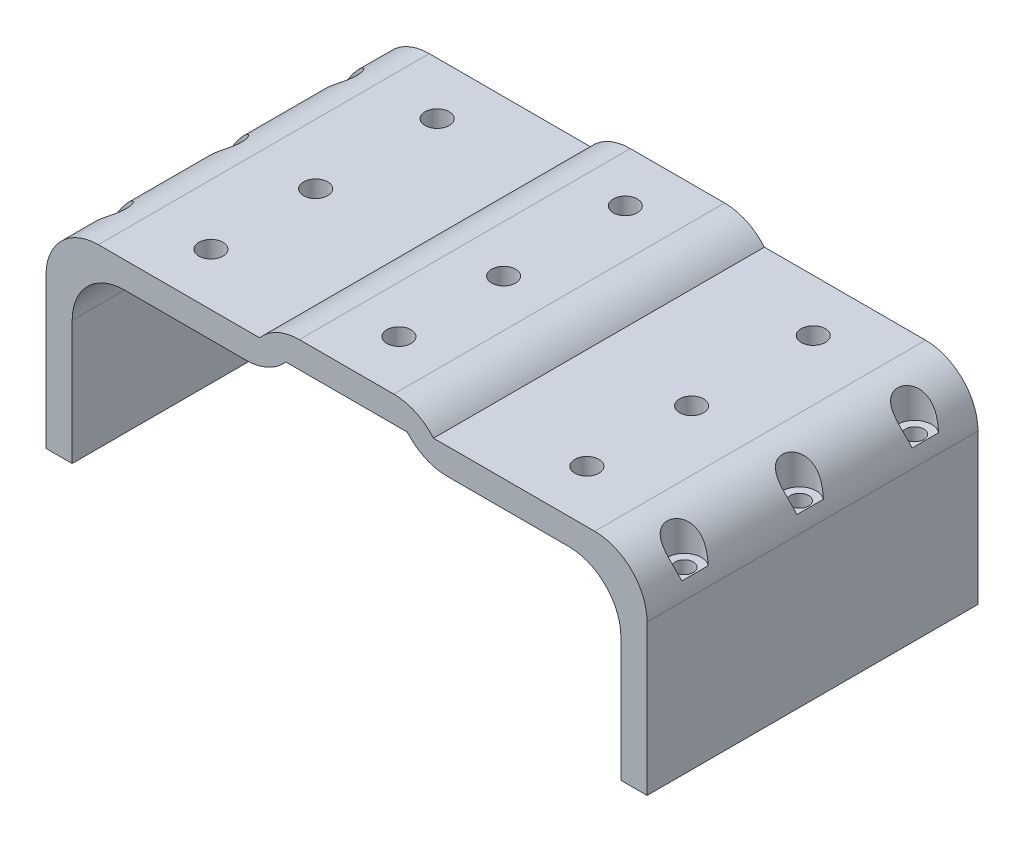
SolidWorks part; units mm, degrees
ref_plane "Front Plane" through (0, 0, 0) normal (0, 0, 1) x (1, 0, 0)
ref_plane "Top Plane" through (0, 0, 0) normal (0, 1, 0) x (1, 0, 0)
ref_plane "Right Plane" through (0, 0, 0) normal (1, 0, 0) x (0, 0, -1)
sketch "Sketch1" plane through (0, 0, 0) normal (0, 0, 1) x (1, 0, 0)
  line L5 (114.8, 0) -> (114.8, 22.5)
  line L7 (0, 22.5) -> (0, 0)
  line L8 (22.5, 22.5) -> (0, 22.5)
  line L9 (22.5, 22.5) -> (40.7918, 22.5)
  line L10 (40.7918, 22.5) -> (40.7918, 26)
  line L11 (40.7918, 26) -> (74.0082, 26)
  line L12 (74.0082, 26) -> (74.0082, 22.5)
  line L13 (74.0082, 22.5) -> (92.3, 22.5)
  line L14 (92.3, 22.5) -> (114.8, 22.5)
  line L15 (5, 0) -> (5, 17.5)
  line L16 (5, 17.5) -> (22.5, 17.5)
  line L17 (22.5, 17.5) -> (45.7918, 17.5)
  line L18 (45.7918, 17.5) -> (45.7918, 21)
  line L19 (45.7918, 21) -> (57.4, 21)
  line L20 (57.4, 21) -> (69.0082, 21)
  line L21 (69.0082, 21) -> (69.0082, 17.5)
  line L22 (69.0082, 17.5) -> (92.3, 17.5)
  line L23 (92.3, 17.5) -> (109.8, 17.5)
  line L24 (109.8, 17.5) -> (109.8, 0)
  line L25 (5, 0) -> (109.8, 0) construction
  line L26 (114.8, 0) -> (114.8, -16.2)
  line L27 (114.8, -16.2) -> (109.8, -16.2)
  line L28 (109.8, -16.2) -> (109.8, 0)
  line L29 (5, 0) -> (5, -16.2)
  line L30 (5, -16.2) -> (0, -16.2)
  line L31 (0, -16.2) -> (0, 0)
  circle A0 centre (22.5, 0) radius 17.5 construction
  circle A1 centre (92.3, 0) radius 17.5 construction
  circle A2 centre (57.4, 0) radius 21 construction
  dimension "D3" = 35
  dimension "D4" = 42
  dimension "D1" = 5
  dimension "D2" = 114.8
  dimension "D5" = 5
  dimension "D6" = 5
  dimension "D7" = 38.7
  dimension "D8" = 5
extrude "Boss-Extrude1" add sketch "Sketch1" along normal blind 63.2 contours L16 L17 L18 L19 L20 L21 L22 L23 L24 L28 L27 L26 L5 L14 L13 L12 L11 L10 L9 L8 L7 L31 L30 L29 L15
fillet "Fillet1" radius 10 4 edges at (109.8, 17.5, 31.6) (5, 17.5, 31.6) (114.8, 22.5, 31.6) (0, 22.5, 31.6)
fillet "Fillet2" radius 10 2 edges at (40.7918, 26, 31.6) (74.0082, 26, 31.6)
fillet "Fillet3" radius 10 2 edges at (45.7918, 17.5, 31.6) (69.0082, 17.5, 31.6)
sketch "Sketch2" plane through (0, 26, 0) normal (0, 1, 0) x (1, 0, 0)
  line L0 (57.4, 0) -> (57.4, -63.2) construction
  line L1 (48.3912, 0) -> (66.4088, 0) construction
  line L2 (48.3912, -63.2) -> (66.4088, -63.2) construction
  line L3 (21.5, 0) -> (21.5, -63.2) construction
  line L5 (0, -63.2) -> (10, -63.2) construction
  line L6 (93.3, 0) -> (93.3, -63.2) construction
  line L7 (104.8, -63.2) -> (114.8, -63.2) construction
  line L13 (40.7918, -63.2) -> (10, -63.2) construction
  line L14 (10, 0) -> (40.7918, 0) construction
  line L15 (21.5, -10) -> (122.7833, -10) construction
  line L16 (21.5, -33.2) -> (122.7833, -33.2) construction
  line L17 (21.5, -53.2) -> (122.7833, -53.2) construction
  circle A0 centre (57.4, -9.9642) radius 2.3
  circle A1 centre (57.4, -33.2) radius 2.3
  circle A2 centre (57.4, -53.2) radius 2.3
  circle A3 centre (21.5, -10) radius 2.3
  circle A4 centre (93.3, -9.9642) radius 2.3
  circle A5 centre (93.3, -33.2) radius 2.3
  circle A6 centre (93.3, -53.2) radius 2.3
  circle A7 centre (21.5, -53.2) radius 2.3
  circle A8 centre (21.5, -33.2) radius 2.3
  point P16 (109.8, -63.2)
  point P39 (5, -63.2)
  dimension "D1" = 4.6
  dimension "D2" = 16.5
  dimension "D3" = 16.5
  dimension "D4" = 10
  dimension "D5" = 20
  dimension "D6" = 10
extrude "Cut-Extrude1" cut sketch "Sketch2" against normal up to next
sketch "Sketch3" plane through (0, -16.2, 0) normal (0, -1, 0) x (1, 0, 0)
  line L0 (2.5, 0) -> (2.5, 63.2) construction
  line L3 (57.4, 63.2) -> (57.4, -4.5196) construction
  line L4 (45.7918, 63.2) -> (69.0082, 63.2) construction
  line L5 (5, 0) -> (0, 0) construction
  circle A0 centre (2.5, 31.6) radius 1.75
  circle A1 centre (2.5, 53.6) radius 1.75
  circle A2 centre (2.5, 9.6) radius 1.75
  circle A3 centre (112.3, 9.6) radius 1.75
  circle A4 centre (112.3, 53.6) radius 1.75
  circle A5 centre (112.3, 31.6) radius 1.75
  point P2 (2.5, 0)
  dimension "D1" = 3.5
  dimension "D2" = 22
  dimension "D3" = 22
extrude "Cut-Extrude2" cut sketch "Sketch3" against normal through all
sketch "Sketch4" plane through (0, 22.5, 0) normal (0, 1, 0) x (1, 0, 0)
  line L0 (57.4, 0) -> (57.4, -72.1972) construction
  line L1 (48.3912, 0) -> (66.4088, 0) construction
  circle A0 centre (2.5, -9.6) radius 3.25
  circle A1 centre (2.5, -31.6) radius 3.25
  circle A2 centre (2.5, -53.6) radius 3.25
  circle A3 centre (112.3, -53.6) radius 3.25
  circle A4 centre (112.3, -31.6) radius 3.25
  circle A5 centre (112.3, -9.6) radius 3.25
  dimension "D1" = 6.5
extrude "Cut-Extrude3" cut sketch "Sketch4" against normal blind 7
